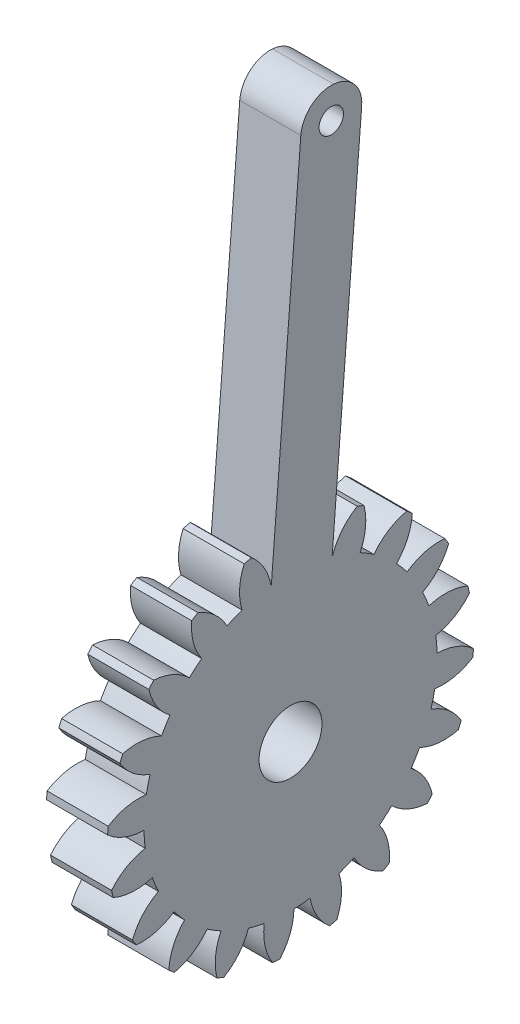
SolidWorks part; units mm, degrees
ref_plane "前视基准面" through (0, 0, 0) normal (0, 0, 1) x (1, 0, 0)
ref_plane "上视基准面" through (0, 0, 0) normal (0, 1, 0) x (1, 0, 0)
ref_plane "右视基准面" through (0, 0, 0) normal (1, 0, 0) x (0, 0, -1)
other "Configuration Table"
sketch "草图1" plane through (0, 0, 0) normal (1, 0, 0) x (0, 0, -1)
  line L0 (0, 0) -> (50000, 0) construction
  line L1 (0, 27) -> (0, -50000) construction
  line L2 (0, 0) -> (8.2085, 22.5526) construction
  line L3 (0, 0) -> (3922.9548, 49845.8667) construction
  arc A0 (-7.9429, 22.6475) -> (-10.3978, 21.6307) centre (0, 0) ccw
  arc A5 (1.751, 29.9489) -> (-0.5557, 23.9936) centre (8.6776, 23.8416) ccw
  arc A6 (2.9556, 29.8541) -> (4.3022, 23.6112) centre (-4.8411, 24.9056) cw
  arc A7 (2.9556, 29.8541) -> (1.751, 29.9489) centre (0, 0) ccw
  arc A8 (12.0363, 27.4796) -> (11.3879, 21.1262) centre (3.092, 25.1826) cw
  arc A9 (12.0363, 27.4796) -> (10.92, 27.942) centre (0, 0) ccw
  arc A10 (10.92, 27.942) -> (6.886, 22.9909) centre (15.6204, 19.9932) ccw
  arc A11 (19.9389, 22.4152) -> (17.3589, 16.5731) centre (10.7225, 22.9946) cw
  arc A12 (19.9389, 22.4152) -> (19.0201, 23.1999) centre (0, 0) ccw
  arc A13 (19.0201, 23.1999) -> (13.6535, 19.7378) centre (21.0341, 14.1877) ccw
  arc A14 (25.8897, 15.1566) -> (21.6307, 10.3978) centre (17.3035, 18.5557) cw
  arc A15 (25.8897, 15.1566) -> (25.2583, 16.1869) centre (0, 0) ccw
  arc A16 (25.2583, 16.1869) -> (19.0846, 14.5526) centre (24.3888, 6.9934) ccw
  arc A17 (29.3062, 6.4145) -> (23.7851, 3.2046) centre (22.1906, 12.3004) cw
  arc A18 (29.3062, 6.4145) -> (29.0241, 7.5894) centre (0, 0) ccw
  arc A19 (29.0241, 7.5894) -> (22.6475, 7.9429) centre (25.3562, -0.8855) ccw
  arc A20 (29.8541, -2.9556) -> (23.6112, -4.3022) centre (24.9056, 4.8411) cw
  arc A21 (29.8541, -2.9556) -> (29.9489, -1.751) centre (0, 0) ccw
  arc A22 (29.9489, -1.751) -> (23.9936, 0.5557) centre (23.8416, -8.6776) ccw
  arc A23 (27.4796, -12.0363) -> (21.1262, -11.3879) centre (25.1826, -3.092) cw
  arc A24 (27.4796, -12.0363) -> (27.942, -10.92) centre (0, 0) ccw
  arc A25 (27.942, -10.92) -> (22.9909, -6.886) centre (19.9932, -15.6204) ccw
  arc A26 (22.4152, -19.9389) -> (16.5731, -17.3589) centre (22.9946, -10.7225) cw
  arc A27 (22.4152, -19.9389) -> (23.1999, -19.0201) centre (0, 0) ccw
  arc A28 (23.1999, -19.0201) -> (19.7378, -13.6535) centre (14.1877, -21.0341) ccw
  arc A29 (15.1566, -25.8897) -> (10.3978, -21.6307) centre (18.5557, -17.3035) cw
  arc A30 (15.1566, -25.8897) -> (16.1869, -25.2583) centre (0, 0) ccw
  arc A31 (16.1869, -25.2583) -> (14.5526, -19.0846) centre (6.9934, -24.3888) ccw
  arc A32 (6.4145, -29.3062) -> (3.2046, -23.7851) centre (12.3004, -22.1906) cw
  arc A33 (6.4145, -29.3062) -> (7.5894, -29.0241) centre (0, 0) ccw
  arc A34 (7.5894, -29.0241) -> (7.9429, -22.6475) centre (-0.8855, -25.3562) ccw
  arc A35 (-2.9556, -29.8541) -> (-4.3022, -23.6112) centre (4.8411, -24.9056) cw
  arc A36 (-2.9556, -29.8541) -> (-1.751, -29.9489) centre (0, 0) ccw
  arc A37 (-1.751, -29.9489) -> (0.5557, -23.9936) centre (-8.6776, -23.8416) ccw
  arc A38 (-12.0363, -27.4796) -> (-11.3879, -21.1262) centre (-3.092, -25.1826) cw
  arc A39 (-12.0363, -27.4796) -> (-10.92, -27.942) centre (0, 0) ccw
  arc A40 (-10.92, -27.942) -> (-6.886, -22.9909) centre (-15.6204, -19.9932) ccw
  arc A41 (-19.9389, -22.4152) -> (-17.3589, -16.5731) centre (-10.7225, -22.9946) cw
  arc A42 (-19.9389, -22.4152) -> (-19.0201, -23.1999) centre (0, 0) ccw
  arc A43 (-19.0201, -23.1999) -> (-13.6535, -19.7378) centre (-21.0341, -14.1877) ccw
  arc A44 (-25.8897, -15.1566) -> (-21.6307, -10.3978) centre (-17.3035, -18.5557) cw
  arc A45 (-25.8897, -15.1566) -> (-25.2583, -16.1869) centre (0, 0) ccw
  arc A46 (-25.2583, -16.1869) -> (-19.0846, -14.5526) centre (-24.3888, -6.9934) ccw
  arc A47 (-29.3062, -6.4145) -> (-23.7851, -3.2046) centre (-22.1906, -12.3004) cw
  arc A48 (-29.3062, -6.4145) -> (-29.0241, -7.5894) centre (0, 0) ccw
  arc A49 (-29.0241, -7.5894) -> (-22.6475, -7.9429) centre (-25.3562, 0.8855) ccw
  arc A50 (-29.8541, 2.9556) -> (-23.6112, 4.3022) centre (-24.9056, -4.8411) cw
  arc A51 (-29.8541, 2.9556) -> (-29.9489, 1.751) centre (0, 0) ccw
  arc A52 (-29.9489, 1.751) -> (-23.9936, -0.5557) centre (-23.8416, 8.6776) ccw
  arc A53 (-27.4796, 12.0363) -> (-21.1262, 11.3879) centre (-25.1826, 3.092) cw
  arc A54 (-27.4796, 12.0363) -> (-27.942, 10.92) centre (0, 0) ccw
  arc A55 (-27.942, 10.92) -> (-22.9909, 6.886) centre (-19.9932, 15.6204) ccw
  arc A56 (-22.4152, 19.9389) -> (-16.5731, 17.3589) centre (-22.9946, 10.7225) cw
  arc A57 (-22.4152, 19.9389) -> (-23.1999, 19.0201) centre (0, 0) ccw
  arc A58 (-23.1999, 19.0201) -> (-19.7378, 13.6535) centre (-14.1877, 21.0341) ccw
  arc A59 (-15.1566, 25.8897) -> (-10.3978, 21.6307) centre (-18.5557, 17.3035) cw
  arc A60 (-15.1566, 25.8897) -> (-16.1869, 25.2583) centre (0, 0) ccw
  arc A61 (-16.1869, 25.2583) -> (-14.5526, 19.0846) centre (-6.9934, 24.3888) ccw
  arc A62 (-6.4145, 29.3062) -> (-3.2046, 23.7851) centre (-12.3004, 22.1906) cw
  arc A63 (-6.4145, 29.3062) -> (-7.5894, 29.0241) centre (0, 0) ccw
  arc A64 (-7.5894, 29.0241) -> (-7.9429, 22.6475) centre (0.8855, 25.3562) ccw
  arc A65 (-14.5526, 19.0846) -> (-16.5731, 17.3589) centre (0, 0) ccw
  arc A66 (-19.7378, 13.6535) -> (-21.1262, 11.3879) centre (0, 0) ccw
  arc A67 (-22.9909, 6.886) -> (-23.6112, 4.3022) centre (0, 0) ccw
  arc A68 (-23.9936, -0.5557) -> (-23.7851, -3.2046) centre (0, 0) ccw
  arc A69 (-19.0846, -14.5526) -> (-17.3589, -16.5731) centre (0, 0) ccw
  arc A70 (-22.6475, -7.9429) -> (-21.6307, -10.3978) centre (0, 0) ccw
  arc A71 (-13.6535, -19.7378) -> (-11.3879, -21.1262) centre (0, 0) ccw
  arc A72 (0.5557, -23.9936) -> (3.2046, -23.7851) centre (0, 0) ccw
  arc A73 (7.9429, -22.6475) -> (10.3978, -21.6307) centre (0, 0) ccw
  arc A74 (14.5526, -19.0846) -> (16.5731, -17.3589) centre (0, 0) ccw
  arc A75 (19.7378, -13.6535) -> (21.1262, -11.3879) centre (0, 0) ccw
  arc A76 (22.9909, -6.886) -> (23.6112, -4.3022) centre (0, 0) ccw
  arc A77 (23.9936, 0.5557) -> (23.7851, 3.2046) centre (0, 0) ccw
  arc A78 (22.6475, 7.9429) -> (21.6307, 10.3978) centre (0, 0) ccw
  arc A79 (19.0846, 14.5526) -> (17.3589, 16.5731) centre (0, 0) ccw
  arc A80 (13.6535, 19.7378) -> (11.3879, 21.1262) centre (0, 0) ccw
  arc A81 (6.886, 22.9909) -> (4.3022, 23.6112) centre (0, 0) ccw
  arc A82 (-0.5557, 23.9936) -> (-3.2046, 23.7851) centre (0, 0) ccw
  arc A83 (-6.886, -22.9909) -> (-4.3022, -23.6112) centre (0, 0) ccw
  point P134 (0, 0)
  dimension "D1" = 48
  dimension "D3" = 20
  dimension "D2" = 20
  dimension "D5" = 4.5
extrude "凸台-拉伸1" add sketch "草图1" along normal blind 10
sketch "草图2" plane through (10, 0, 0) normal (1, 0, 0) x (0, 0, -1)
  line L0 (0, 0) -> (0, 50000) construction
  line L5 (0, 0) -> (3922.9548, 49845.8667) construction
  line L6 (2.0767, 90.1149) -> (-4.9846, 0.3923)
  line L7 (-4.9846, 0.3923) -> (4.9846, -0.3923)
  line L8 (4.9846, -0.3923) -> (12.0459, 89.3303)
  line L9 (12.0459, 89.3303) -> (2.0767, 90.1149)
  dimension "D1" = 4.5
  dimension "D2" = 5
  dimension "D3" = 5
  dimension "D4" = 90
extrude "凸台-拉伸2" add sketch "草图2" against normal blind 10
fillet "圆角1" radius 5 2 edges at (5, 89.3303, -12.0459) (5, 90.1149, -2.0767)
sketch "草图3" plane through (10, 0, 0) normal (1, 0, 0) x (0, 0, -1)
  circle A0 centre (0, 0) radius 5.15
  dimension "D1" = 10.3
extrude "切除-拉伸1" cut sketch "草图3" against normal blind 10
sketch "草图4" plane through (10, 0, 0) normal (1, 0, 0) x (0, 0, -1)
  circle A0 centre (6.669, 84.738) radius 2
  dimension "D1" = 4
extrude "切除-拉伸2" cut sketch "草图4" against normal blind 10
